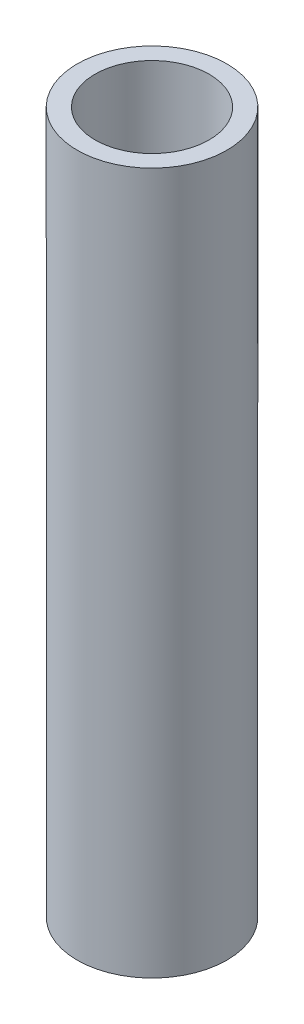
SolidWorks part; units mm, degrees
material "AISI 316 Stainless Steel Sheet (SS)"
ref_plane "Front Plane" through (0, 0, 0) normal (0, 0, 1) x (1, 0, 0)
ref_plane "Top Plane" through (0, 0, 0) normal (0, 1, 0) x (1, 0, 0)
ref_plane "Right Plane" through (0, 0, 0) normal (1, 0, 0) x (0, 0, -1)
sketch "Sketch1" plane through (0, 0, 0) normal (0, 1, 0) x (1, 0, 0)
  circle A0 centre (0, 0) radius 1.05
  circle A1 centre (0, 0) radius 0.8
  dimension "D1" = 2.1
  dimension "D2" = 1.6
extrude "Boss-Extrude1" add sketch "Sketch1" along normal offset from surface (9.841 mm away) 5 contours A1 | A0 offset beyond the face yes
